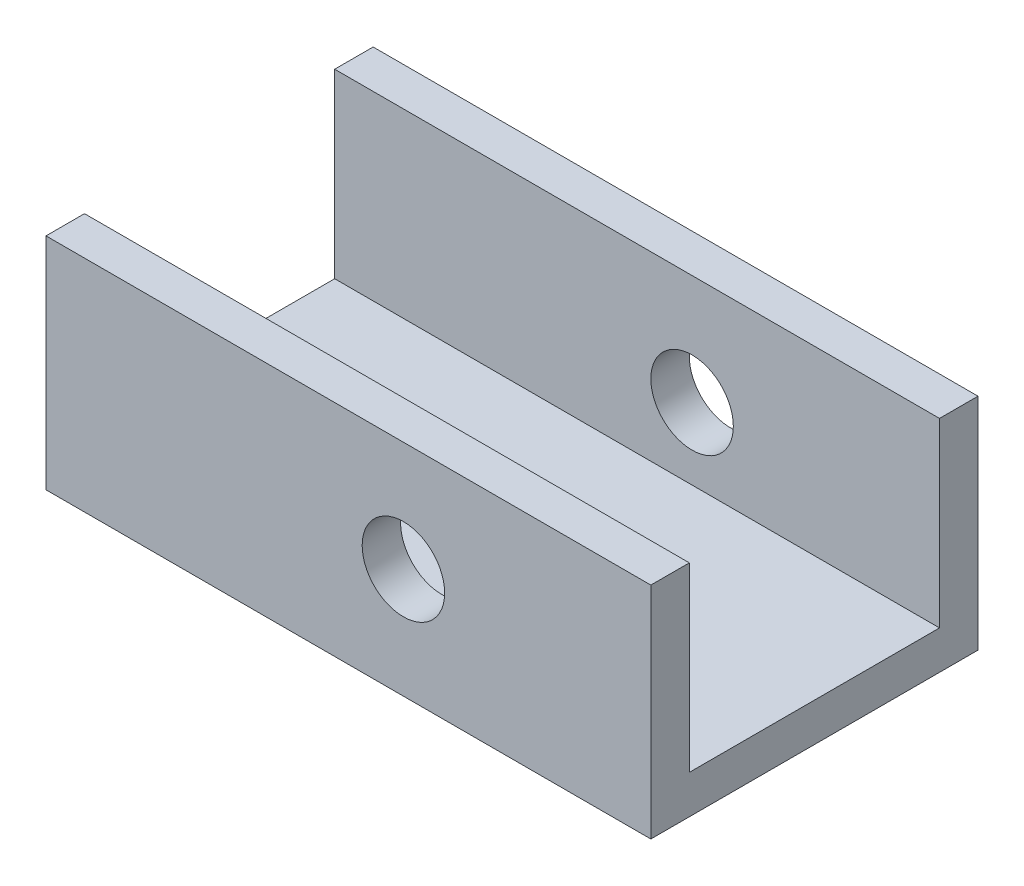
SolidWorks part; units mm, degrees
ref_plane "Спереди" through (0, 0, 0) normal (0, 0, 1) x (1, 0, 0)
ref_plane "Сверху" through (0, 0, 0) normal (0, 1, 0) x (1, 0, 0)
ref_plane "Справа" through (0, 0, 0) normal (1, 0, 0) x (0, 0, -1)
other "Configuration Table"
sketch "Эскиз1" plane through (0, 0, 0) normal (0, 1, 0) x (1, 0, 0)
  line L0 (0, 10.5) -> (22, 10.5)
  line L1 (0, 0) -> (22, 0)
  line L2 (0, 0) -> (0, 11.9)
  line L3 (0, 11.9) -> (22, 11.9)
  line L4 (22, 0) -> (22, 11.9)
  line L5 (22, 1.4) -> (0, 1.4)
  dimension "D1" = 22
  dimension "D2" = 11.9
  dimension "D3" = 1.4
  dimension "D4" = 1.4
extrude "Bottom" add sketch "Эскиз1" along normal blind 1.4 contours L5 L4 L0 L2 | L0 L4 L3 L2 | L4 L5 L2 L1 region at (11, 0, -11.2) region at (11, 0, -5.95) region at (11, 0, -0.7)
extrude "Бобышка-Вытянуть2" add sketch "Эскиз1<3>" along normal blind 8 contours L0 L4 L3 L2 | L4 L5 L2 L1 region at (11, 0, -11.2) region at (11, 0, -0.7)
sketch "Эскиз1<3>" plane through (0, 0, 0) normal (0, 1, 0) x (1, 0, 0) same geometry as "Эскиз1"
sketch "Эскиз2" plane through (0, 0, 0) normal (0, 0, 1) x (1, 0, 0)
  line L0 (0, 4) -> (22, 4) construction
  line L1 (0, 8) -> (0, 0) construction
  line L2 (22, 8) -> (22, 0) construction
  line L3 (11, -2.418) -> (11, 10.418) construction
  circle A0 centre (13, 4) radius 1.5
  point P9 (11, 4)
  point P11 (0, 0)
  point P12 (0, 0)
  point P13 (0, 0)
  point P14 (0, 0)
  dimension "D1" = 3
  dimension "D2" = 13
extrude "Вырез-Вытянуть1" cut sketch "Эскиз2" against normal through all both and the other way through all
equation "\"D4@Эскиз1\"=\"D3@Эскиз1\""
